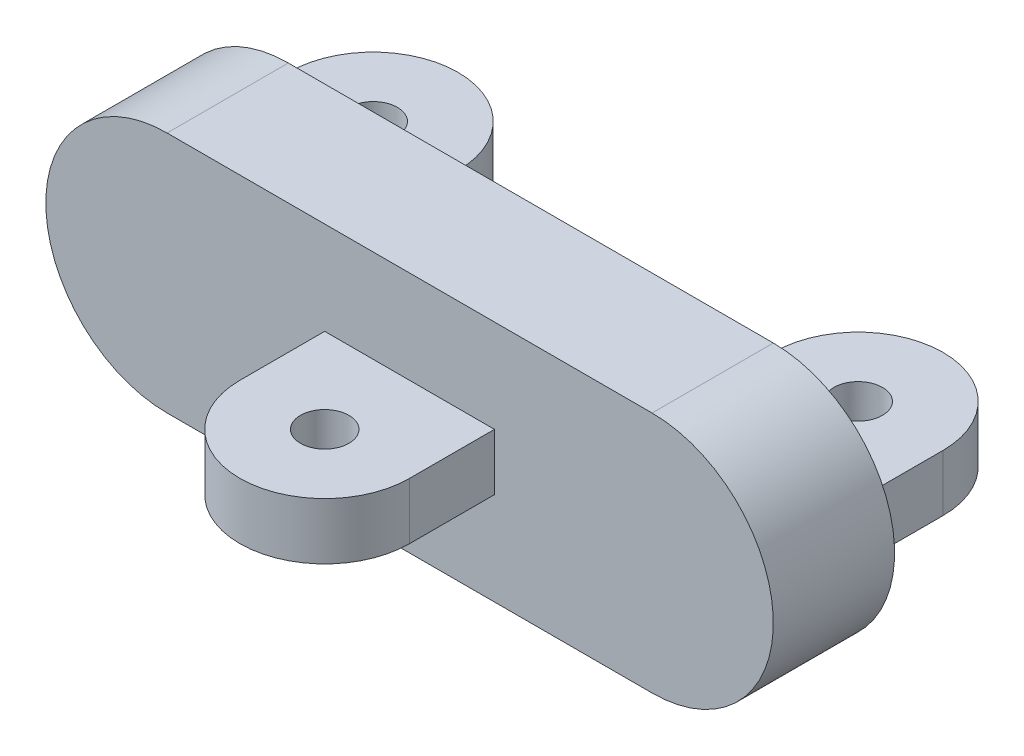
SolidWorks part; units mm, degrees
ref_plane "Front Plane" through (0, 0, 0) normal (0, 0, 1) x (1, 0, 0)
ref_plane "Top Plane" through (0, 0, 0) normal (0, 1, 0) x (1, 0, 0)
ref_plane "Right Plane" through (0, 0, 0) normal (1, 0, 0) x (0, 0, -1)
sketch "Sketch2" plane through (0, 0, 0) normal (0, 0, 1) x (1, 0, 0)
  line L1 (-10, -5) -> (10, -5)
  line L3 (-10, 5) -> (10, 5)
  line L5 (-10, -5) -> (10, 5) construction
  line L6 (-10, 5) -> (10, -5) construction
  arc A0 (-10, -5) -> (-10, 5) centre (-10, 0) cw
  arc A1 (10, -5) -> (10, 5) centre (10, 0) ccw
  point P0 (0, 0)
  dimension "D1" = 20
  dimension "D2" = 10
extrude "Boss-Extrude1" add sketch "Sketch2" against normal blind 5
sketch "Sketch3" plane through (0, 0, 0) normal (0, 0, 1) x (1, 0, 0)
  line L1 (-3.5, -1.1667) -> (3.5, -1.1667)
  line L2 (-3.5, -1.1667) -> (-3.5, 1.1667)
  line L3 (-3.5, 1.1667) -> (3.5, 1.1667)
  line L4 (3.5, -1.1667) -> (3.5, 1.1667)
  line L5 (-3.5, -1.1667) -> (3.5, 1.1667) construction
  line L6 (-3.5, 1.1667) -> (3.5, -1.1667) construction
  point P0 (0, 0)
  dimension "D1" = 2.3333
  dimension "D2" = 7
extrude "Boss-Extrude2" add sketch "Sketch3" along normal blind 3.5
sketch "Sketch6" plane through (0, 0, 3.5) normal (0, 0, 1) x (1, 0, 0)
  line L0 (0, 1.1667) -> (0, -1.1667)
  line L1 (3.5, 1.1667) -> (-3.5, 1.1667) construction
  line L2 (-3.5, -1.1667) -> (3.5, -1.1667) construction
  line L3 (0, -1.1667) -> (-3.5, -1.1667)
  line L4 (-3.5, -1.1667) -> (-3.5, 1.1667)
  line L5 (-3.5, 1.1667) -> (0, 1.1667)
revolve "Revolve1" add sketch "Sketch6" angle 180 about L0 reverse direction yes
sketch "Sketch7" plane through (0, 1.1667, 0) normal (0, 1, 0) x (1, 0, 0)
  line L0 (3.5, 0) -> (-3.5, 0) construction
  circle A0 centre (0, -3.5) radius 1
  dimension "D1" = 2
  dimension "D2" = 3.5
extrude "Cut-Extrude1" cut sketch "Sketch7" against normal up to next contours A0
sketch "Sketch8" plane through (0, 0, -5) normal (0, 0, -1) x (-1, 0, 0)
  line L1 (0, 5.5) -> (0, -5.5) construction
  line L2 (-13.5, 1.165) -> (-6.5, 1.165)
  line L3 (-13.5, 1.165) -> (-13.5, -1.165)
  line L4 (-13.5, -1.165) -> (-6.5, -1.165)
  line L5 (-6.5, 1.165) -> (-6.5, -1.165)
  line L6 (-13.5, 1.165) -> (-6.5, -1.165) construction
  line L7 (-13.5, -1.165) -> (-6.5, 1.165) construction
  line L8 (13.5, -1.165) -> (6.5, -1.165)
  line L9 (6.5, 1.165) -> (6.5, -1.165)
  line L10 (13.5, 1.165) -> (6.5, 1.165)
  line L11 (13.5, 1.165) -> (13.5, -1.165)
  point P0 (-10, 0)
  dimension "D1" = 2.33
  dimension "D2" = 7
extrude "Boss-Extrude3" add sketch "Sketch8" along normal blind 3.5
sketch "Sketch9" plane through (0, 0, -8.5) normal (0, 0, -1) x (-1, 0, 0)
  line L0 (-13.5, -1.165) -> (-6.5, -1.165) construction
  line L1 (-13.5, 1.165) -> (-10, 1.165)
  line L2 (-13.5, 1.165) -> (-13.5, -1.165)
  line L3 (-13.5, -1.165) -> (-10, -1.165)
  line L4 (-10, 1.165) -> (-10, -1.165)
  line L5 (6.5, -1.165) -> (13.5, -1.165) construction
  line L6 (6.5, 1.165) -> (10, 1.165)
  line L7 (6.5, 1.165) -> (6.5, -1.165)
  line L8 (6.5, -1.165) -> (10, -1.165)
  line L9 (10, 1.165) -> (10, -1.165)
revolve "Revolve2" add sketch "Sketch9" angle 180 about L4 region at (11.75, 0, -8.5) reverse direction yes
revolve "Revolve3" add sketch "Sketch9<3>" angle 180 about L9 region at (-8.25, 0, -8.5) reverse direction yes
sketch "Sketch9<3>" plane through (0, 0, -8.5) normal (0, 0, -1) x (-1, 0, 0) same geometry as "Sketch9"
sketch "Sketch11" plane through (0, 1.165, 0) normal (0, 1, 0) x (1, 0, 0)
  line L0 (0, -5.5) -> (0, 5.5) construction
  circle A0 centre (-10, 8.5) radius 1
  circle A1 centre (10, 8.5) radius 1
  dimension "D1" = 2
extrude "Cut-Extrude2" cut sketch "Sketch11" against normal up to next
